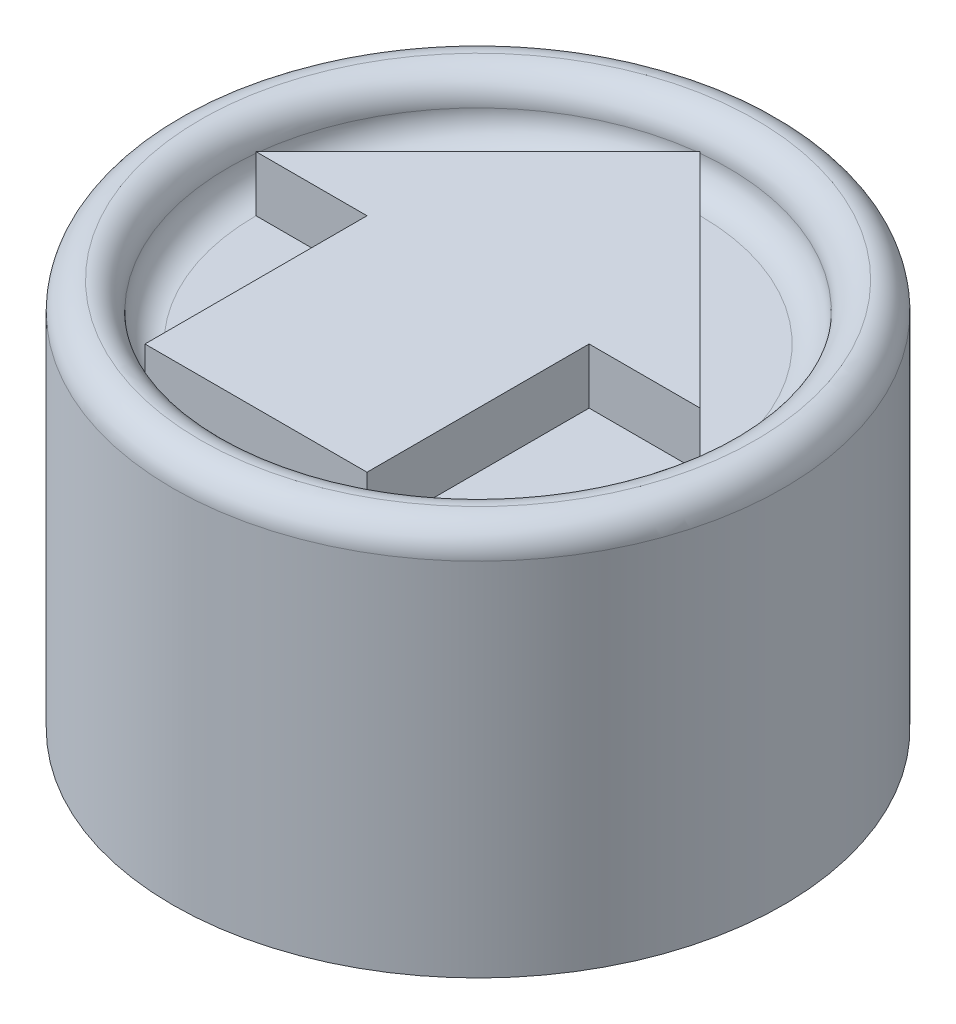
SolidWorks part; units mm, degrees
ref_plane "Спереди" through (0, 0, 0) normal (0, 0, 1) x (1, 0, 0)
ref_plane "Сверху" through (0, 0, 0) normal (0, 1, 0) x (1, 0, 0)
ref_plane "Справа" through (0, 0, 0) normal (1, 0, 0) x (0, 0, -1)
sketch "Эскиз1" plane through (0, 0, 0) normal (0, 1, 0) x (1, 0, 0)
  circle A0 centre (0, 0) radius 5.5
extrude "Бобышка-Вытянуть1" add sketch "Эскиз1" along normal blind 7
fillet "Скругление1" radius 0.5 1 edges at (0, 7, 5.5)
sketch "Эскиз2" plane through (0, 7, 0) normal (0, 1, 0) x (1, 0, 0)
  circle A0 centre (0, 0) radius 4.5
extrude "Вырез-Вытянуть1" cut sketch "Эскиз2" against normal blind 1
fillet "Скругление2" radius 0.5 1 edges at (0, 7, 4.5)
sketch "Эскиз3" plane through (0, 6, 0) normal (0, 1, 0) x (1, 0, 0)
  line L0 (-1000, 0) -> (49000, 0) construction
  line L1 (0, -1000) -> (0, 49000) construction
  line L2 (2, -1000) -> (2, 49000) construction
  line L3 (-2, -1000) -> (-2, 49000) construction
  line L4 (-1000, -4) -> (49000, -4) construction
  line L5 (-1000, 4) -> (49000, 4) construction
  line L6 (-4, -1000) -> (-4, 49000) construction
  line L7 (4, -1000) -> (4, 49000) construction
  line L8 (0, 4) -> (-4, 0)
  line L9 (-4, 0) -> (-2, 0)
  line L10 (-2, 0) -> (-2, -4)
  line L11 (-2, -4) -> (2, -4)
  line L12 (2, -4) -> (2, 0)
  line L13 (2, 0) -> (4, 0)
  line L14 (4, 0) -> (0, 4)
extrude "Бобышка-Вытянуть2" add sketch "Эскиз3" along normal blind 1
fillet "Скругление3" radius 0.5 1 edges at (0, 6, 4.5)
sketch "Эскиз5" plane through (0, 0, 0) normal (0, -1, 0) x (1, 0, 0)
  line L0 (0, -1000) -> (0, 49000) construction
  line L1 (-1000, 0) -> (49000, 0) construction
  line L2 (-2, -2) -> (2, -2)
  line L3 (2, -2) -> (2, 2)
  line L4 (-2, 2) -> (2, 2)
  line L5 (-2, -2) -> (-2, 2)
  line L7 (-2, -1000) -> (-2, 49000) construction
  line L8 (2, -1000) -> (2, 49000) construction
  line L9 (-1000, 2) -> (49000, 2) construction
  line L10 (-1000, -2) -> (49000, -2) construction
  dimension "D1" = 2
  dimension "D2" = 2
extrude "Вырез-Вытянуть2" cut sketch "Эскиз5" against normal blind 3
